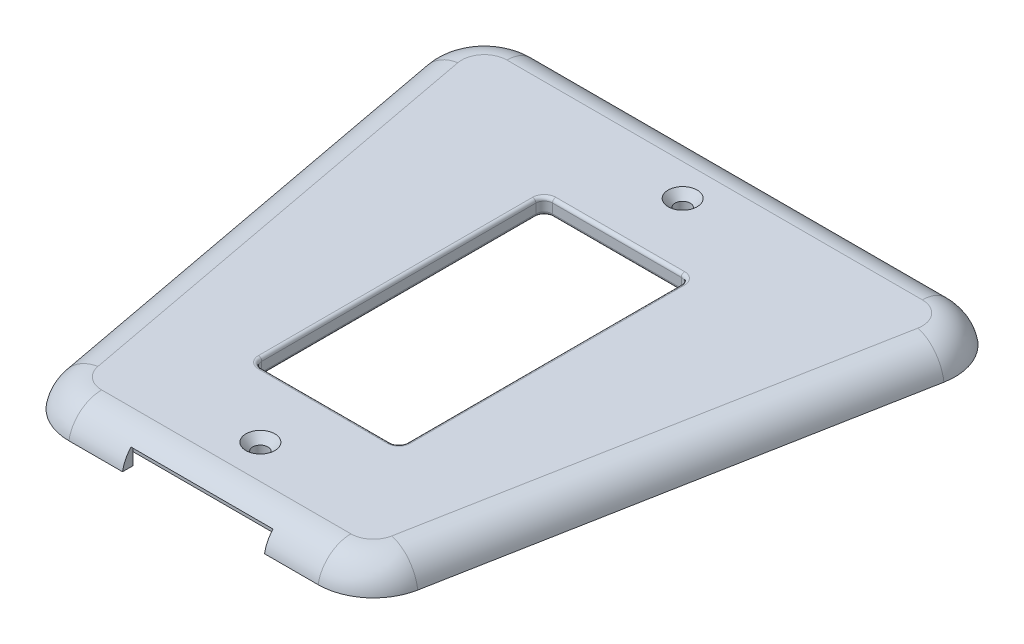
SolidWorks part; units mm, degrees
note: The reader was unsure of these and kept them because the rebuilt part matched: shared geometry of "Sketch9<3>", "Sketch8<3>".
ref_plane "Front Plane" through (0, 0, 0) normal (0, 0, 1) x (1, 0, 0)
ref_plane "Top Plane" through (0, 0, 0) normal (0, 1, 0) x (1, 0, 0)
ref_plane "Right Plane" through (0, 0, 0) normal (1, 0, 0) x (0, 0, -1)
sketch "Sketch1" plane through (0, 0, 0) normal (0, 1, 0) x (1, 0, 0)
  line L3 (-20.9924, 111.9595) -> (-1.9424, 10.3595)
  line L4 (39.1151, 127) -> (39.1151, 0) construction
  line L5 (-8.5099, 127) -> (86.7401, 127)
  line L6 (10.5401, 0) -> (67.6901, 0)
  line L7 (99.2225, 111.9595) -> (80.1725, 10.3595)
  arc A0 (10.5401, 0) -> (-1.9424, 10.3595) centre (10.5401, 12.7) cw
  arc A1 (-8.5099, 127) -> (-20.9924, 111.9595) centre (-8.5099, 114.3) ccw
  arc A2 (67.6901, 0) -> (80.1725, 10.3595) centre (67.6901, 12.7) ccw
  arc A3 (86.7401, 127) -> (99.2225, 111.9595) centre (86.7401, 114.3) cw
  point P7 (0, 0)
  dimension "D1" = 12.7
  dimension "D2" = 57.15
  dimension "D3" = 95.25
  dimension "D4" = 127
extrude "Boss-Extrude1" add sketch "Sketch1" along normal blind 6.35
shell "Shell1" thickness 2.413
fillet "Fillet1" radius 7.62 8 edges at (75.8007, 6.35, -2.9272) (39.1151, 6.35, 0) (2.4294, 6.35, -2.9272) (-11.4674, 6.35, -61.1595) (-18.2827, 6.35, -122.4107) (39.1151, 6.35, -127) (96.5128, 6.35, -122.4107) (89.6975, 6.35, -61.1595)
sketch "Sketch2" plane through (0, 6.35, 0) normal (0, 1, 0) x (1, 0, 0)
  line L0 (34.3526, 76.4404) -> (43.8776, 76.4404)
  line L1 (43.8776, 76.4404) -> (43.8776, 51.0404)
  line L2 (34.3526, 76.4404) -> (34.3526, 51.0404)
  line L3 (34.3526, 51.0404) -> (43.8776, 51.0404)
  line L4 (39.1151, 112.1528) -> (39.1151, 15.328) construction
  line L7 (39.1151, 76.4404) -> (39.1151, 51.0404) construction
  line L8 (-4.307, 63.7404) -> (82.5371, 63.7404) construction
  line L9 (-13.6077, 113.3442) -> (5.4423, 11.7442) construction
  line L10 (72.7878, 11.7442) -> (91.8378, 113.3442) construction
  circle A0 centre (39.1151, 112.1528) radius 2.3812
  circle A1 centre (39.1151, 15.328) radius 2.3812
  point P10 (39.1151, 63.7404)
  point P13 (39.1151, 63.7404)
  dimension "D3" = 4.7625
  dimension "D1" = 9.525
  dimension "D2" = 25.4
  dimension "D4" = 96.8248
extrude "Cut-Extrude2" [suppressed] cut sketch "Sketch2" against normal blind 5.588 contours L2 L3 L1 L0
sketch "Sketch4" plane through (0, 3.937, 0) normal (0, -1, 0) x (1, 0, 0)
  circle A0 centre (39.1151, -112.1528) radius 4.445
  circle A1 centre (39.1151, -15.328) radius 4.445
  circle A2 centre (39.1151, -15.328) radius 2.3813 construction
  circle A3 centre (39.1151, -112.1528) radius 2.3813 construction
  dimension "D1" = 8.89
  dimension "D2" = 8.89
extrude "Boss-Extrude2" add sketch "Sketch4" along normal blind 1.27
hole_wizard "CSK for #3 Flat Head Machine Screw (100)1" positions "3DSketch3" profile "Sketch7" countersink size "#3" standard "ANSI Inch"
sketch3d "3DSketch3"
  point P0 (39.1151, 6.35, -112.1528)
  point P6 (39.1151, 6.35, -112.1528)
  point P8 (32.4472, 6.35, -10.0076)
  point P11 (39.1151, 6.35, -112.1528)
  point P13 (39.1151, 6.35, -15.328)
sketch "Sketch7" plane through (39.1151, 6.35, -112.1528) normal (1, 0, 0) x (0, 0, 1)
  line L0 (0, 0) -> (0, 6.35)
  line L1 (0, 6.35) -> (1.7526, 6.35)
  line L2 (1.7526, 6.35) -> (1.7526, 1.8116)
  line L3 (1.7526, 1.8116) -> (3.3274, 0)
  line L5 (3.3274, 0) -> (0, 0)
  line L6 (-1.7526, 1.8116) -> (-3.3274, 0) construction
  line L11 (0, -6.35) -> (0, 107.95) construction
  dimension "Thru Hole Dia." = 3.5052
  dimension "Thru Hole Depth" = 6.35
  dimension "Near C'Sink Dia." = 6.6548
  dimension "Near C'Sink Angle" = 82
sketch "Sketch8" plane through (0, 6.35, 0) normal (0, 1, 0) x (1, 0, 0)
  line L0 (39.1151, 112.1528) -> (39.1151, 15.328) construction
  line L3 (39.1151, 63.7404) -> (82.5371, 63.7404) construction
  line L4 (72.7878, 11.7442) -> (91.8378, 113.3442) construction
  line L6 (24.3513, 97.0779) -> (53.8788, 97.0779)
  line L7 (22.4463, 95.1729) -> (22.4463, 32.3079)
  line L8 (24.3513, 30.4029) -> (53.8788, 30.4029)
  line L9 (55.7838, 95.1729) -> (55.7838, 32.3079)
  line L10 (22.4463, 97.0779) -> (55.7838, 30.4029) construction
  line L11 (22.4463, 30.4029) -> (55.7838, 97.0779) construction
  arc A0 (22.4463, 32.3079) -> (24.3513, 30.4029) centre (24.3513, 32.3079) ccw
  arc A1 (53.8788, 30.4029) -> (55.7838, 32.3079) centre (53.8788, 32.3079) ccw
  arc A2 (53.8788, 97.0779) -> (55.7838, 95.1729) centre (53.8788, 95.1729) cw
  arc A3 (24.3513, 97.0779) -> (22.4463, 95.1729) centre (24.3513, 95.1729) ccw
  circle A4 centre (39.1151, 112.1528) radius 1.7526 construction
  dimension "D3" = 1.905
  dimension "D1" = 33.3375
  dimension "D2" = 66.675
extrude "Cut-Extrude3" cut sketch "Sketch8" against normal blind 5.588 contours L7 A0 L8 A1 L9 A2 L6 A3
sketch "Sketch10" plane through (0, 3.937, 0) normal (0, -1, 0) x (1, 0, 0)
  line L54 (57.3713, -95.1729) -> (57.3713, -32.3079)
  line L55 (53.8788, -28.8154) -> (24.3513, -28.8154)
  line L56 (20.8588, -32.3079) -> (20.8588, -95.1729)
  line L57 (24.3513, -98.6654) -> (53.8788, -98.6654)
  line L58 (57.3713, -95.1729) -> (57.3713, -32.3079)
  line L59 (53.8788, -28.8154) -> (24.3513, -28.8154)
  line L60 (20.8588, -32.3079) -> (20.8588, -95.1729)
  line L61 (24.3513, -98.6654) -> (53.8788, -98.6654)
  arc A44 (53.8788, -98.6654) -> (57.3713, -95.1729) centre (53.8788, -95.1729) ccw
  arc A45 (57.3713, -32.3079) -> (53.8788, -28.8154) centre (53.8788, -32.3079) ccw
  arc A46 (24.3513, -28.8154) -> (20.8588, -32.3079) centre (24.3513, -32.3079) ccw
  arc A47 (20.8588, -95.1729) -> (24.3513, -98.6654) centre (24.3513, -95.1729) ccw
  arc A48 (53.8788, -98.6654) -> (57.3713, -95.1729) centre (53.8788, -95.1729) ccw
  arc A49 (57.3713, -32.3079) -> (53.8788, -28.8154) centre (53.8788, -32.3079) ccw
  arc A50 (24.3513, -28.8154) -> (20.8588, -32.3079) centre (24.3513, -32.3079) ccw
  arc A51 (20.8588, -95.1729) -> (24.3513, -98.6654) centre (24.3513, -95.1729) ccw
  dimension "D1" = 1.5875
sketch "Sketch9" plane through (0, 3.937, 0) normal (0, -1, 0) x (1, 0, 0)
  line L0 (13.0801, -2.413) -> (13.0801, -7.7311)
  line L1 (13.0801, -7.7311) -> (65.1501, -7.7311)
  line L2 (65.1501, -7.7311) -> (65.1501, -2.413)
  line L4 (65.1501, -2.413) -> (13.0801, -2.413)
  line L5 (15.6201, -2.413) -> (15.6201, -5.1911)
  line L6 (15.6201, -5.1911) -> (62.6101, -5.1911)
  line L7 (62.6101, -5.1911) -> (62.6101, -2.413)
  line L8 (39.1151, -2.413) -> (39.1151, -30.4029) construction
  line L9 (53.8788, -30.4029) -> (24.3513, -30.4029) construction
  line L11 (10.5401, -2.413) -> (67.6901, -2.413) construction
  line L12 (22.8337, -2.413) -> (22.8337, 0)
  line L13 (10.5401, 0) -> (67.6901, 0) construction
  line L14 (22.8337, 0) -> (55.3965, 0)
  line L15 (55.3965, 0) -> (55.3965, -2.413)
  point P2 (39.1151, -5.1911)
  point P12 (39.1151, -7.7311)
  point P23 (39.1151, 0)
  line M28 (67.6901, -2.413) -> (10.5401, -2.413)
  dimension "D1" = 46.99
  dimension "D2" = 2.54
  dimension "D3" = 2.54
  dimension "D4" = 2.7781
  dimension "D5" = 32.5628
extrude "Cut-Extrude4" cut sketch "Sketch9" along normal blind 3.97 contours L15 L14 L12 L4 M28
extrude "Boss-Extrude3" add sketch "Sketch9<3>" along normal up to surface (3.937 mm away) contours L8 L6 L5 L4 L0 L1 | L6 L8 L1 L2 L7 M28 up to face at (39.1151, 0, -50.3168)
sketch "Sketch9<3>" plane through (0, 3.937, 0) normal (0, -1, 0) x (1, 0, 0) same geometry as "Sketch9"
extrude "Boss-Extrude4" add sketch "Sketch10" along normal blind 1.27
extrude "Cut-Extrude5" cut sketch "Sketch8<3>" against normal through all contours L8 A1 L9 A2 L6 A3 L7 A0
sketch "Sketch8<3>" plane through (0, 6.35, 0) normal (0, 1, 0) x (1, 0, 0) same geometry as "Sketch8"
fillet "Fillet2" radius 0.762 26 edges at (56.3484, 2.667, -29.8383) (57.3713, 2.667, -63.7404) (56.3484, 2.667, -97.6424) (39.1151, 2.667, -98.6654) (21.8817, 2.667, -97.6424) (20.8588, 2.667, -63.7404) (21.8817, 2.667, -29.8383) (39.1151, 2.667, -28.8154) (39.1151, 2.667, -116.5978) (39.1151, 2.667, -19.773) (23.0043, 6.35, -96.5199) (39.1151, 6.35, -97.0779) (55.2259, 6.35, -96.5199) (55.7838, 6.35, -63.7404) (55.2259, 6.35, -30.9608) (39.1151, 6.35, -30.4029) (23.0043, 6.35, -30.9608) (55.2259, 2.667, -96.5199) (55.7838, 2.667, -63.7404) (55.2259, 2.667, -30.9608) (39.1151, 2.667, -30.4029) (23.0043, 2.667, -30.9608) (22.4463, 2.667, -63.7404) (23.0043, 2.667, -96.5199) (22.4463, 6.35, -63.7404) (39.1151, 2.667, -97.0779)
